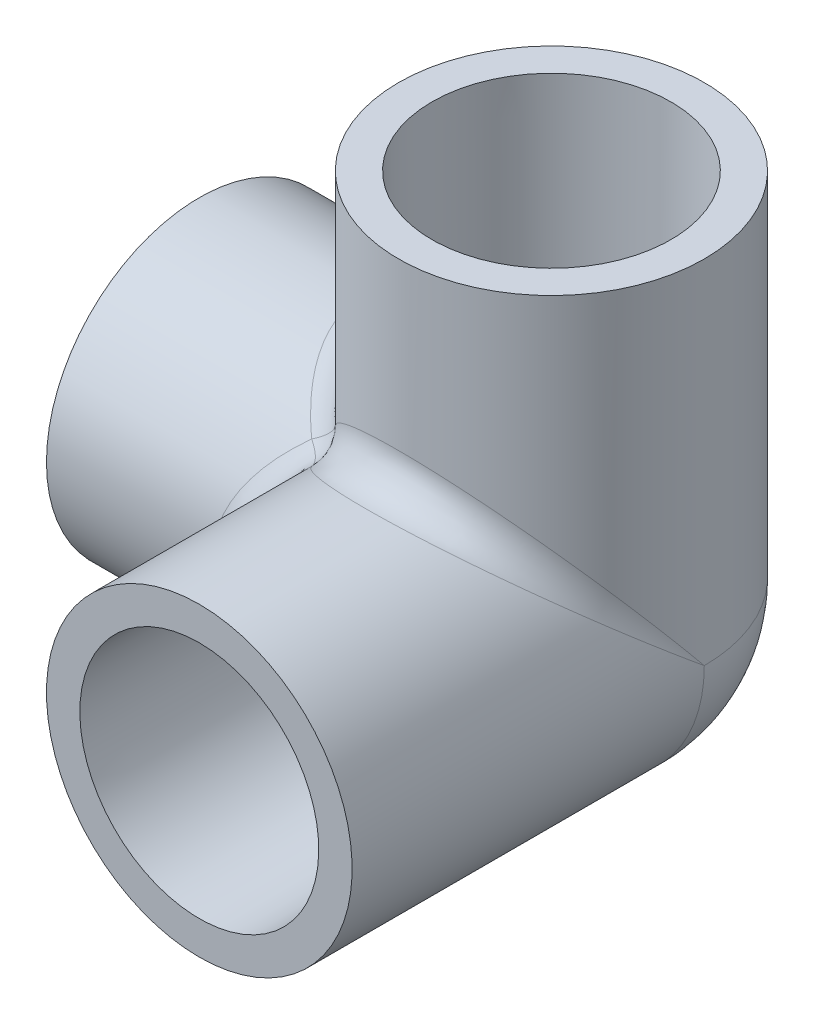
SolidWorks part; units mm, degrees
ref_plane "Front Plane" through (0, 0, 0) normal (0, 0, 1) x (1, 0, 0)
ref_plane "Top Plane" through (0, 0, 0) normal (0, 1, 0) x (1, 0, 0)
ref_plane "Right Plane" through (0, 0, 0) normal (1, 0, 0) x (0, 0, -1)
sketch "Sketch0" plane through (0, 0, 0) normal (0, 0, 1) x (1, 0, 0)
  line L0 (-31.75, 0) -> (0, 0) construction
  line L1 (0, 0) -> (0, 31.75) construction
  line L2 (-12.7, 0) -> (0, 0) construction
  line L3 (0, 0) -> (0, 12.7) construction
  line L4 (-31.75, 13.7795) -> (-31.75, -13.7795) construction
  line L5 (-12.7, 10.6172) -> (-31.75, 10.7696) construction
  line L6 (-12.7, 10.6172) -> (-12.7, -10.6172) construction
  line L7 (-12.7, -10.6172) -> (-31.75, -10.7696) construction
  line L8 (-31.75, 10.7696) -> (-31.75, -10.7696) construction
  line L9 (-13.7795, 31.75) -> (13.7795, 31.75) construction
  line L10 (-10.7696, 31.75) -> (10.7696, 31.75) construction
  line L11 (10.7696, 31.75) -> (10.6172, 12.7) construction
  line L12 (10.6172, 12.7) -> (-10.6172, 12.7) construction
  line L13 (-10.6172, 12.7) -> (-10.7696, 31.75) construction
  line L14 (-12.7, 7.8994) -> (-12.7, -7.8994) construction
  line L18 (-7.8994, 12.7) -> (7.8994, 12.7) construction
sketch "Sketch1" plane through (0, 0, 0) normal (0, 0, 1) x (1, 0, 0)
  line L0 (-31.75, 0) -> (13.7795, 0)
  line L1 (-31.75, 0) -> (-31.75, -13.7795)
  line L2 (-31.75, -13.7795) -> (0, -13.7795)
  arc A0 (0, -13.7795) -> (13.7795, 0) centre (0, 0) ccw
  dimension "D1" = 45.5295
revolve "Revolve1" add sketch "Sketch1" angle 360 about L0
sketch "Sketch2" plane through (0, 0, 0) normal (0, 0, 1) x (1, 0, 0)
  line L0 (13.7795, 31.75) -> (0, 31.75)
  line L4 (0, 31.75) -> (0, -13.7795)
  line L5 (13.7795, 0) -> (13.7795, 31.75)
  arc A0 (13.7795, 0) -> (0, -13.7795) centre (0, 0) cw
revolve "Revolve2" add sketch "Sketch2" angle 360 about L4
sketch "Sketch3" plane through (0, 0, 0) normal (1, 0, 0) x (0, 0, -1)
  line L0 (13.7795, 0) -> (-31.75, 0)
  line L1 (-31.75, 0) -> (-31.75, -13.7795)
  line L2 (-31.75, -13.7795) -> (0, -13.7795)
  arc A0 (0, -13.7795) -> (13.7795, 0) centre (0, 0) ccw
  dimension "D1" = 45.5295
revolve "Revolve3" add sketch "Sketch3" angle 360 about L0
sketch "Sketch4" plane through (0, 0, 0) normal (0, 0, 1) x (1, 0, 0)
  line L0 (-31.75, 0) -> (7.8994, 0)
  line L1 (-31.75, 13.7795) -> (-31.75, -13.7795) construction
  line L2 (0, -7.8994) -> (-12.7, -7.8994)
  line L3 (-12.7, -7.8994) -> (-12.7, -10.6172)
  line L4 (-12.7, -10.6172) -> (-31.75, -10.7696)
  line L5 (-31.75, -10.7696) -> (-31.75, 0)
  arc A0 (7.8994, 0) -> (0, -7.8994) centre (0, 0) cw
  dimension "D1" = 19.05
revolve "Cut-Revolve1" cut sketch "Sketch4" angle 360 about L0
sketch "Sketch5" plane through (0, 0, 0) normal (0, 0, 1) x (1, 0, 0)
  line L0 (0, 31.75) -> (0, -7.8994)
  line L1 (7.8994, 0) -> (7.8994, 12.7)
  line L2 (7.8994, 12.7) -> (10.6172, 12.7)
  line L3 (10.6172, 12.7) -> (10.7696, 31.75)
  line L4 (0, 31.75) -> (10.7696, 31.75)
  arc A0 (0, -7.8994) -> (7.8994, 0) centre (0, 0) ccw
revolve "Cut-Revolve2" cut sketch "Sketch5" angle 360 about L0
sketch "Sketch6" plane through (0, 0, 0) normal (1, 0, 0) x (0, 0, -1)
  line L0 (7.8994, 0) -> (-31.75, 0)
  line L1 (-31.75, 0) -> (-31.75, -10.7696)
  line L2 (-31.75, -10.7696) -> (-12.7, -10.6172)
  line L3 (-12.7, -10.6172) -> (-12.7, -7.8994)
  line L4 (-12.7, -7.8994) -> (0, -7.8994)
  line L5 (-7.8994, 0) -> (7.8994, 0) construction
  line L6 (-31.75, 13.7795) -> (-31.75, -13.7795) construction
  arc A0 (0, -7.8994) -> (7.8994, 0) centre (0, 0) ccw
  dimension "D1" = 19.05
revolve "Cut-Revolve3" cut sketch "Sketch6" angle 360 about L0
fillet "Fillet1" radius 3.0099 6 edges at (-12.7306, -5.2732, 12.7306) (5.2732, 12.7306, 12.7306) (-12.7306, 12.7306, -5.2732) (-7.2981, -3.023, 7.2981) (-7.2981, 7.2981, -3.023) (3.023, 7.2981, 7.2981)
equation "\"D1@Sketch3\" = \"D1@Sketch1\""
equation "\"D1@Sketch6\" = \"D1@Sketch4\""
equation "\"D1@Fillet1\" =  ( \"M@Sketch0\" - \"OD A@Sketch0\" )  / 2"
